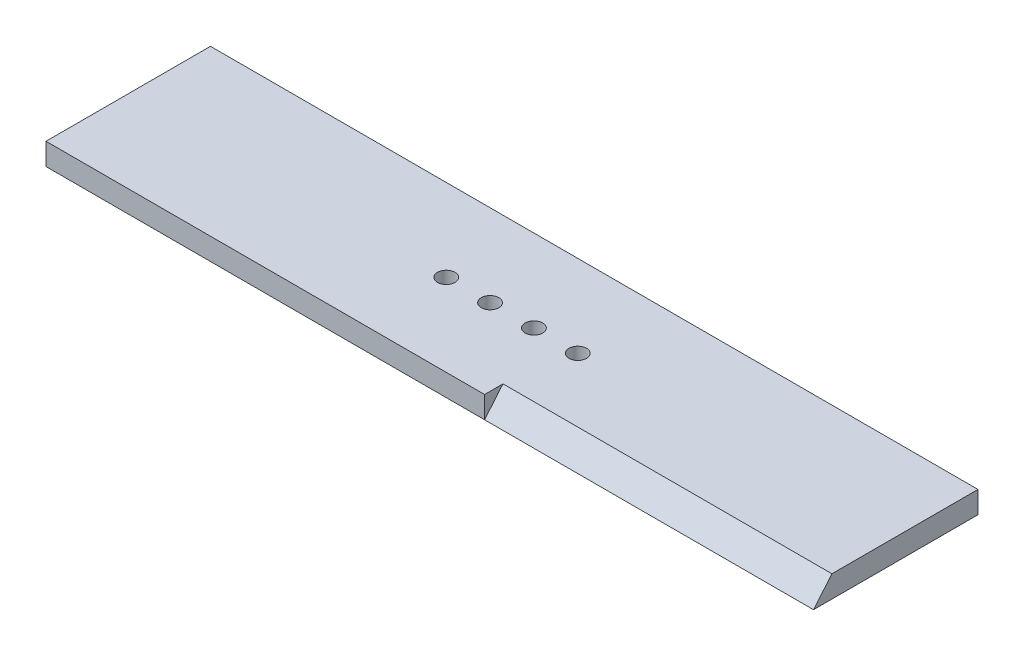
SolidWorks part; units mm, degrees
ref_plane "Front Plane" through (0, 0, 0) normal (0, 0, 1) x (1, 0, 0)
ref_plane "Top Plane" through (0, 0, 0) normal (0, 1, 0) x (1, 0, 0)
ref_plane "Right Plane" through (0, 0, 0) normal (1, 0, 0) x (0, 0, -1)
sketch "Sketch1" plane through (0, 0, 0) normal (0, 1, 0) x (1, 0, 0)
  line L1 (-175, -37.5) -> (175, -37.5)
  line L2 (-175, -37.5) -> (-175, 37.5)
  line L3 (-175, 37.5) -> (175, 37.5)
  line L4 (175, -37.5) -> (175, 37.5)
  line L5 (-175, -37.5) -> (175, 37.5) construction
  line L6 (-175, 37.5) -> (175, -37.5) construction
  point P1 (0, 0)
  dimension "D1" = 350
  dimension "D2" = 75
sketch "Sketch5" plane through (0, 0, 0) normal (0, 1, 0) x (1, 0, 0)
  line L0 (-175, 0) -> (175, 0) construction
  line L1 (-175, -37.5) -> (-175, 37.5) construction
  line L2 (175, -37.5) -> (175, 37.5) construction
  line L3 (0, 37.5) -> (0, -37.5) construction
  line L4 (-175, 37.5) -> (175, 37.5) construction
  line L5 (-175, -37.5) -> (175, -37.5) construction
extrude "Boss-Extrude2" add sketch "Sketch1" along normal mid plane 10
hole_wizard "Ø8.0mm Dowel Hole1" positions "Sketch6" profile "Sketch7" hole size "Ø8.0" standard "ANSI Metric" end condition through all
sketch "Sketch6" plane through (0, 5, 0) normal (0, 1, 0) x (1, 0, 0)
  line L0 (-175, 0) -> (175, 0) construction
  line L1 (-10, 0) -> (10, 0) construction
  line L3 (-30, 0) -> (30, 0) construction
  point P0 (10, 0)
  point P4 (30, 0)
  point P6 (-10, 0)
  point P8 (-30, 0)
  point P15 (0, 0)
  point P25 (0, 0)
  dimension "D1" = 20
  dimension "D2" = 60
sketch "Sketch7" plane through (10, 5, 0) normal (1, 0, 0) x (0, 0, 1)
  line L0 (0, 0) -> (0, 10)
  line L1 (0, 10) -> (4, 10)
  line L2 (4, 10) -> (4, 0)
  line L5 (4, 0) -> (0, 0)
  line L11 (0, -6.35) -> (0, 107.95) construction
  dimension "Thru Hole Dia." = 8
  dimension "Thru Hole Depth" = 10
ref_axis "Axis1" through (0, 0, -46.565) along (0, 0, 1)
ref_axis "Axis2" through (-198.3038, 0, 0) along (1, 0, 0)
ref_point "Point1"
ref_axis "Axis3" through (0, -18.5129, 0) along (0, 1, 0)
ref_plane "Plane1" through (0, 0, 0) normal (0, 1, 0) x (1, 0, 0)
sketch "Sketch10" plane through (175, 0, 0) normal (1, 0, 0) x (0, 0, -1)
  line L0 (-37.5, 5) -> (-37.5, -5)
  line L1 (-37.5, -5) -> (-29.109, 5)
  line L2 (-37.5, 5) -> (37.5, 5) construction
  line L3 (-29.109, 5) -> (-37.5, 5)
  dimension "D1" = 40
extrude "Cut-Extrude3" cut sketch "Sketch10" against normal blind 150
sketch "Sketch11" plane through (-175, 0, 0) normal (-1, 0, 0) x (0, 0, 1)
  line L0 (-37.5, 5) -> (-37.5, -5)
  line L1 (-37.5, -5) -> (-29.109, -5)
  line L2 (-37.5, -5) -> (37.5, -5) construction
  line L3 (-29.109, -5) -> (-37.5, 5)
  dimension "D1" = 40
extrude "Cut-Extrude4" cut sketch "Sketch11" against normal blind 150
